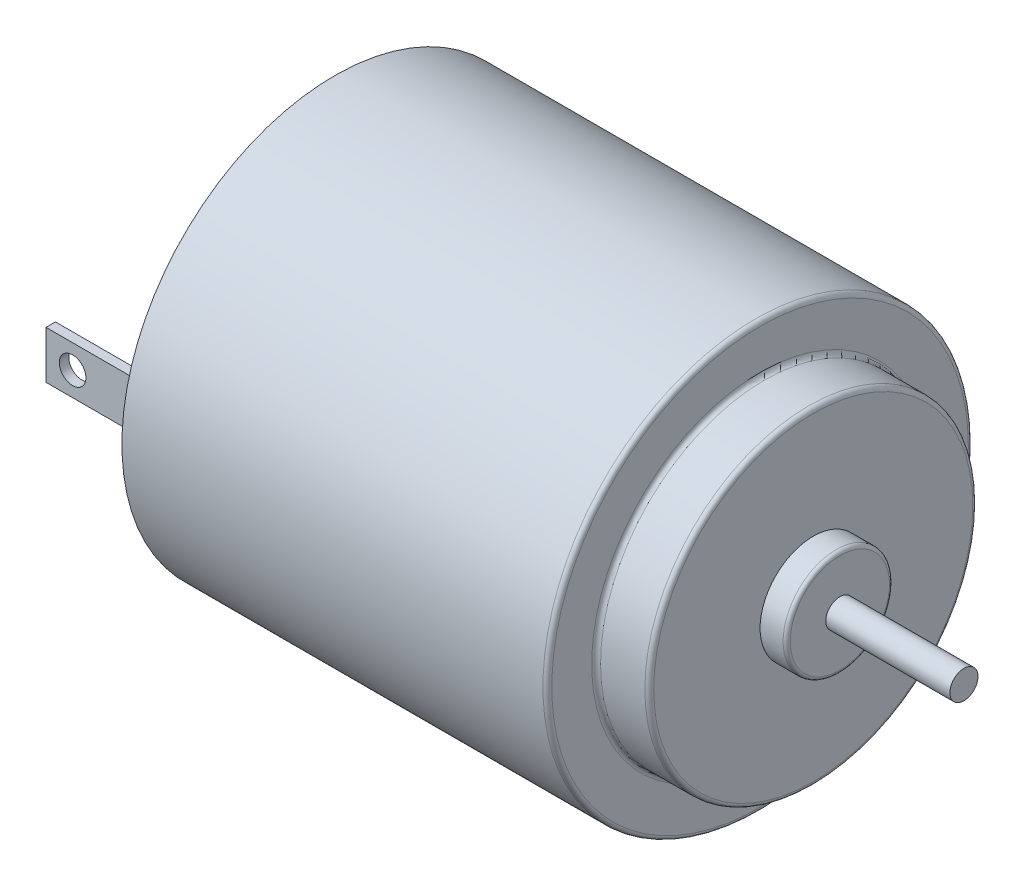
SolidWorks part; units mm, degrees
material "AISI 1020"
ref_plane "Front Plane" through (0, 0, 0) normal (0, 0, 1) x (1, 0, 0)
ref_plane "Top Plane" through (0, 0, 0) normal (0, 1, 0) x (1, 0, 0)
ref_plane "Right Plane" through (0, 0, 0) normal (1, 0, 0) x (0, 0, -1)
sketch "Sketch1" plane through (0, 0, 0) normal (1, 0, 0) x (0, 0, -1)
  circle A0 centre (0, 0) radius 12
  dimension "D1" = 24
extrude "Boss-Extrude1" add sketch "Sketch1" along normal blind 12 and the other way blind 12
sketch "Sketch2" plane through (12, 0, 0) normal (1, 0, 0) x (0, 0, -1)
  circle A0 centre (0, 0) radius 9.25
  dimension "D1" = 18.5
extrude "Boss-Extrude2" add sketch "Sketch2" along normal blind 3
sketch "Sketch3" plane through (15, 0, 0) normal (1, 0, 0) x (0, 0, -1)
  circle A0 centre (0, 0) radius 3
  dimension "D1" = 6
extrude "Boss-Extrude3" add sketch "Sketch3" along normal blind 1.5 contours A0
sketch "Sketch4" plane through (16.5, 0, 0) normal (1, 0, 0) x (0, 0, -1)
  circle A0 centre (0, 0) radius 0.7937
  dimension "D1" = 1.5875
extrude "Boss-Extrude4" add sketch "Sketch4" along normal blind 7
fillet "Fillet1" radius 0.25 3 edges at (15, 0, -9.25) (12, 0, -9.25) (12, 0, -12)
fillet "Fillet2" radius 0.2 1 edges at (16.5, 0, -3)
sketch "Sketch5" plane through (-12, 0, 0) normal (-1, 0, 0) x (0, 0, 1)
  line L1 (9.25, -1.3439) -> (9.7828, -1.3439)
  line L2 (9.25, -1.3439) -> (9.25, 1.3439)
  line L3 (9.25, 1.3439) -> (9.7828, 1.3439)
  line L4 (9.7828, -1.3439) -> (9.7828, 1.3439)
  line L5 (9.25, -1.3439) -> (9.7828, 1.3439) construction
  line L6 (9.25, 1.3439) -> (9.7828, -1.3439) construction
  circle A0 centre (0, 0) radius 12 construction
  point P0 (9.5164, 0)
  dimension "D1" = 9.25
extrude "Boss-Extrude5" add sketch "Sketch5" along normal blind 6.5
mirror "Mirror1" about plane through (0, 0, 0) normal (0, 0, 1) of "Boss-Extrude5"
sketch "Sketch7" plane through (0, 0, 9.7828) normal (0, 0, 1) x (1, 0, 0)
  line L0 (-12, -1.3439) -> (-12, 1.3439) construction
  circle A0 centre (-17, 0) radius 0.75
  dimension "D1" = 1.5
  dimension "D2" = 5
extrude "Cut-Extrude1" cut sketch "Sketch7" against normal through all
